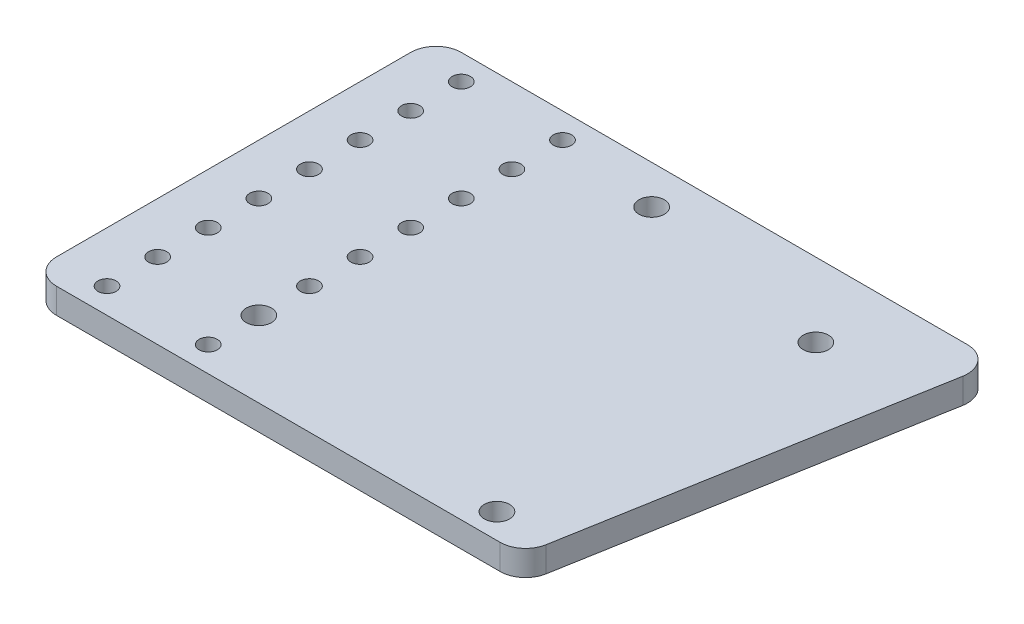
SolidWorks part; units mm, degrees
material "1023 Carbon Steel Sheet (SS)"
ref_plane "Front Plane" through (0, 0, 0) normal (0, 0, 1) x (1, 0, 0)
ref_plane "Top Plane" through (0, 0, 0) normal (0, 1, 0) x (1, 0, 0)
ref_plane "Right Plane" through (0, 0, 0) normal (1, 0, 0) x (0, 0, -1)
sketch "Sketch1" plane through (0, 0, 0) normal (0, 1, 0) x (1, 0, 0)
  line L1 (-65.7024, -47.3531) -> (57.3528, -47.3531)
  line L2 (-65.7024, -47.3531) -> (-65.7024, 54.2469)
  line L3 (-65.7024, 54.2469) -> (75.2676, 54.2469)
  line L4 (57.3528, -47.3531) -> (75.2676, 54.2469)
  line L5 (-65.7024, -47.3531) -> (75.2676, 54.2469) construction
  line L6 (-65.7024, 54.2469) -> (57.3528, -47.3531) construction
  point P0 (0, 0)
  point P6 (69.85, -63.5)
  point P7 (69.85, -63.5)
  point P8 (0, 0)
  point P9 (69.85, 63.5)
  point P10 (69.85, -63.5)
  dimension "D1" = 101.6
  dimension "D2" = 140.97
  dimension "D4" = 80
extrude "Initial Plate" add sketch "Sketch1" along normal blind 6.35
sketch "Sketch3" plane through (0, 6.35, 0) normal (0, 1, 0) x (1, 0, 0)
  line L0 (53.0024, -41.0031) -> (-53.0024, -41.0031) construction
  line L1 (0, 0) -> (0, -41.0031) construction
  line L2 (-65.7024, -47.3531) -> (57.3528, -47.3531) construction
  line L3 (-65.7024, 54.2469) -> (-65.7024, -47.3531) construction
  circle A0 centre (-53.0024, -41.0031) radius 2.286
  circle A1 centre (53.0024, -41.0031) radius 2.286 construction
  circle A2 centre (-27.6024, -41.0031) radius 2.286
  point P4 (0, 0)
  dimension "D1" = 4.572
  dimension "D2" = 6.35
  dimension "D3" = 12.7
  dimension "D4" = 25.4
extrude "Initial Mounting Hole" cut sketch "Sketch3" against normal through all
pattern_linear "Mounting Pattern" count 8 spacing 12.7 along (0, 0, -1) of "Initial Mounting Hole"
sketch "Sketch2" plane through (0, 6.35, 0) normal (0, 1, 0) x (1, 0, 0)
  line L0 (41.5489, -1.8086) -> (-20.9864, 9.2181) construction
  line L1 (-27.6024, -28.3031) -> (-14.3704, 46.7393) construction
  line L2 (34.9329, -39.3297) -> (48.1649, 35.7126) construction
  line L3 (-65.7024, -47.3531) -> (57.3528, -47.3531) construction
  line L4 (-24.7597, 42.1232) -> (-35.2111, 43.9661) construction
  line L5 (-15.1987, -24.0422) -> (-25.6501, -22.1994) construction
  line L6 (-14.3704, 46.7393) -> (-1.8634, 44.5339) construction
  line L7 (34.9329, -39.3297) -> (44.9385, -41.094) construction
  circle A1 centre (-27.6024, -28.3031) radius 3.175
  circle A3 centre (48.1649, 35.7126) radius 3.175
  circle A5 centre (-27.6024, -28.3031) radius 6.35 construction
  circle A6 centre (44.9385, -41.094) radius 3.175
  circle A9 centre (-27.6024, -28.3031) radius 2.286 construction
  circle A10 centre (-1.8634, 44.5339) radius 3.175
  circle A11 centre (-1.8634, 44.5339) radius 6.35 construction
  point P4 (-0.6697, 5.6357)
  point P7 (-20.9864, 9.2181)
  point P10 (41.5489, -1.8086)
  dimension "D5" = 6.35
  dimension "D3" = 12.7
  dimension "D6" = 63.5
  dimension "D2" = 12.7
  dimension "D1" = 63.5
  dimension "D4" = 10
  dimension "D7" = 10.16
  dimension "D8" = 0
extrude "Bearing Stack Holes" cut sketch "Sketch2" against normal through all
fillet "Fillet1" radius 6.35 4 edges at (75.2676, 3.175, -54.2469) (57.3528, 3.175, 47.3531) (-65.7024, 3.175, 47.3531) (-65.7024, 3.175, -54.2469)
